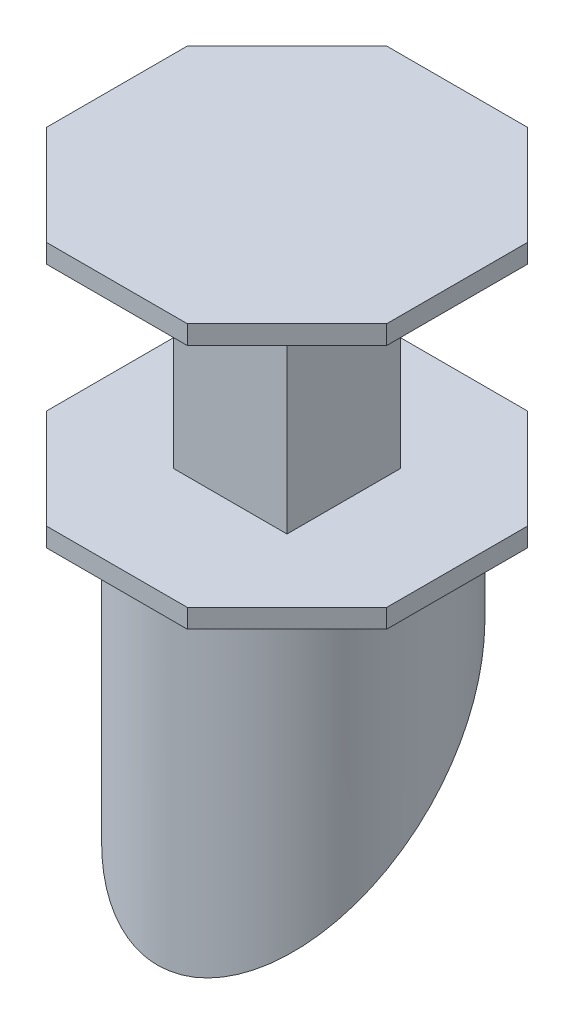
SolidWorks part; units mm, degrees
ref_plane "Front Plane" through (0, 0, 0) normal (0, 0, 1) x (1, 0, 0)
ref_plane "Top Plane" through (0, 0, 0) normal (0, 1, 0) x (1, 0, 0)
ref_plane "Right Plane" through (0, 0, 0) normal (1, 0, 0) x (0, 0, -1)
sketch "Sketch2" plane through (0, 0, 0) normal (1, 0, 0) x (0, 0, -1)
  line L0 (1.0414, 1031.6391) -> (1.0414, 973.3996) construction
  line L1 (1.0414, 1031.6391) -> (-21.7283, 1031.6391)
  line L2 (-21.7283, 1031.6391) -> (-21.7283, 973.3996)
  line L3 (-21.7283, 973.3996) -> (1.0414, 973.3996)
  line L4 (1.0414, 1031.6391) -> (1.0414, 973.3996)
revolve "Revolve1" add sketch "Sketch2" angle 360 about L0
sketch "Sketch3" plane through (0, 0, 0) normal (1, 0, 0) x (0, 0, -1)
  line L0 (-21.7283, 973.3996) -> (23.8111, 1018.9391)
  line L1 (23.8111, 1018.9391) -> (23.8111, 973.3996)
  line L2 (23.8111, 973.3996) -> (-21.7283, 973.3996)
extrude "Cut-Extrude1" cut sketch "Sketch3" against normal through all both and the other way through all
shell "Shell1" thickness 3.175 removed face at (0, 1018.9391, -23.8111)
sketch "Sketch4" plane through (0, 1031.6391, 0) normal (0, 1, 0) x (1, 0, 0)
  line L4 (28.575, 11.8362) -> (11.8362, 28.575)
  line L5 (11.8362, 28.575) -> (-11.8362, 28.575)
  line L6 (-11.8362, 28.575) -> (-28.575, 11.8362)
  line L7 (-28.575, 11.8362) -> (-28.575, -11.8362)
  line L8 (-28.575, -11.8362) -> (-11.8362, -28.575)
  line L9 (-11.8362, -28.575) -> (11.8362, -28.575)
  line L10 (11.8362, -28.575) -> (28.575, -11.8362)
  line L11 (28.575, -11.8362) -> (28.575, 11.8362)
  circle A0 centre (0, 0) radius 28.575 construction
  dimension "D1" = 57.15
extrude "Boss-Extrude1" add sketch "Sketch4" along normal blind 3.175
sketch "Sketch5" plane through (0, 1034.8141, 0) normal (0, 1, 0) x (1, 0, 0)
  line L1 (9.525, 9.525) -> (-9.525, 9.525)
  line L2 (9.525, 9.525) -> (9.525, -9.525)
  line L3 (9.525, -9.525) -> (-9.525, -9.525)
  line L4 (-9.525, 9.525) -> (-9.525, -9.525)
  line L5 (0, -9.525) -> (0, 9.525) construction
  line L6 (9.525, 0) -> (-9.525, 0) construction
  point P0 (0, 0)
  dimension "D1" = 19.05
extrude "Boss-Extrude2" add sketch "Sketch5" along normal blind 38.1
sketch "Sketch6" plane through (0, 1072.9141, 0) normal (0, 1, 0) x (1, 0, 0)
  line L0 (-11.8362, 28.575) -> (-28.575, 11.8362) construction
  line L1 (-28.575, -11.8362) -> (-11.8362, -28.575)
  line L2 (-11.8362, -28.575) -> (11.8362, -28.575)
  line L3 (11.8362, -28.575) -> (28.575, -11.8362)
  line L4 (28.575, -11.8362) -> (28.575, 11.8362)
  line L5 (28.575, 11.8362) -> (11.8362, 28.575)
  line L6 (11.8362, 28.575) -> (-11.8362, 28.575)
  line L7 (-11.8362, 28.575) -> (-28.575, 11.8362)
  line L8 (-28.575, 11.8362) -> (-28.575, -11.8362)
  circle A0 centre (0, 0) radius 28.575 construction
extrude "Boss-Extrude3" add sketch "Sketch6" along normal blind 3.175
